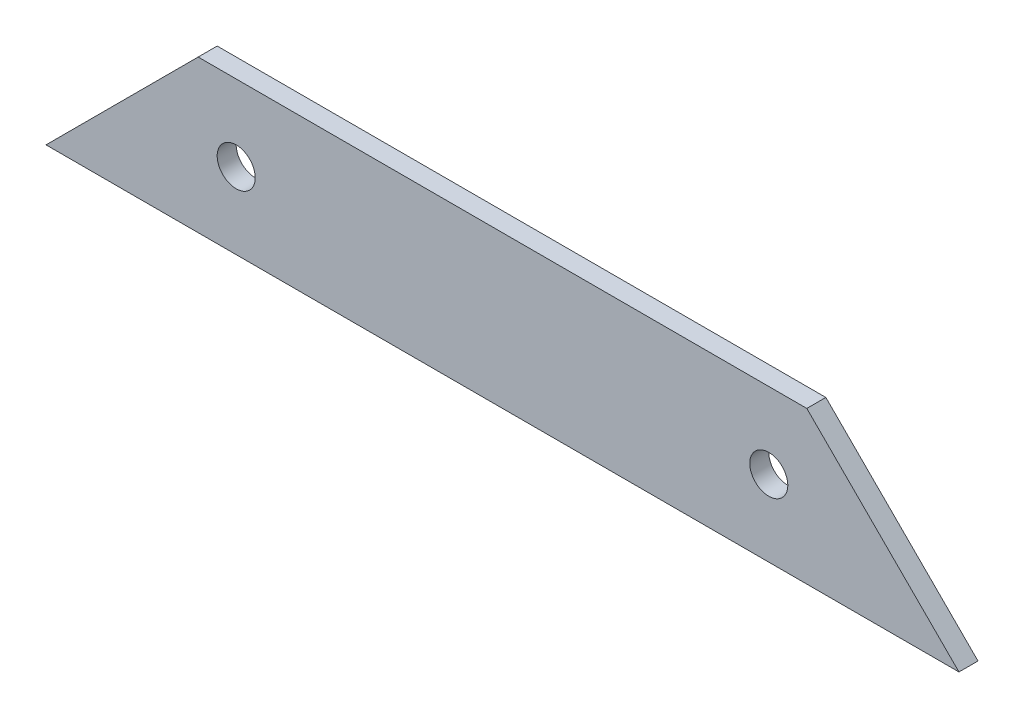
SolidWorks part; units mm, degrees
material "6061 Alloy"
ref_plane "Front Plane" through (0, 0, 0) normal (0, 0, 1) x (1, 0, 0)
ref_plane "Top Plane" through (0, 0, 0) normal (0, 1, 0) x (1, 0, 0)
ref_plane "Right Plane" through (0, 0, 0) normal (1, 0, 0) x (0, 0, -1)
ref_axis "Axis1" through (0, -67.7, 0) along (0, 1, 0)
sketch "Sketch3" plane through (0, 0, 0) normal (0, 0, 1) x (1, 0, 0)
  line L0 (50.8, 0) -> (-50.8, 0)
  line L1 (-50.8, 0) -> (-76.2, -25.4)
  line L2 (-76.2, -25.4) -> (76.2, -25.4)
  line L3 (0, -67.7) -> (0, 42.3) construction
  line L4 (0, 0) -> (0, -25.4) construction
  line L5 (50.8, 0) -> (76.2, -25.4)
  circle A0 centre (-44.45, -12.7) radius 3.175
  circle A1 centre (44.45, -12.7) radius 3.175
  dimension "D4" = 31.75
  dimension "D5" = 6.35
  dimension "D1" = 50.8
  dimension "D2" = 25.4
  dimension "D3" = 12.7
extrude "Boss-Extrude1" add sketch "Sketch3" along normal blind 3.175
